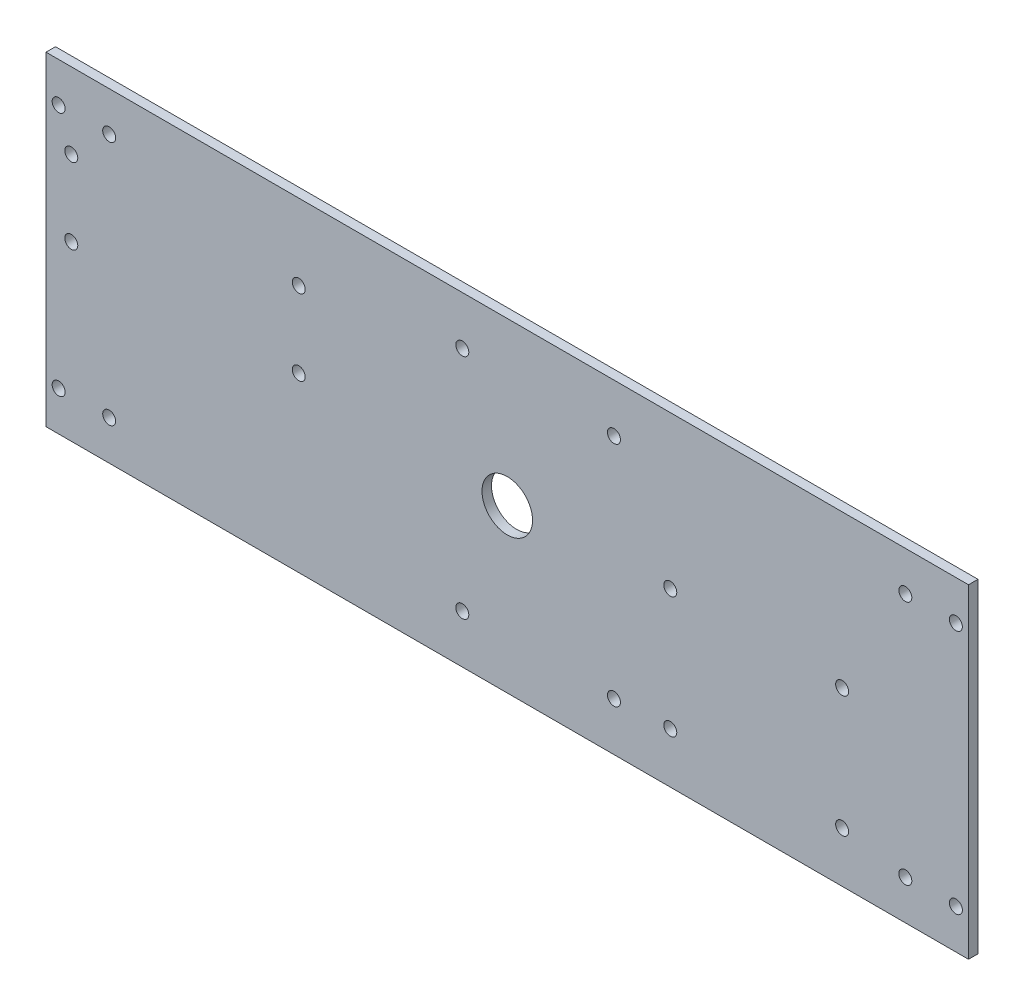
SolidWorks part; units mm, degrees
material "E-Glass Fiber"
ref_plane "Front Plane" through (0, 0, 0) normal (0, 0, 1) x (1, 0, 0)
ref_plane "Top Plane" through (0, 0, 0) normal (0, 1, 0) x (1, 0, 0)
ref_plane "Right Plane" through (0, 0, 0) normal (1, 0, 0) x (0, 0, -1)
sketch "Sketch1" plane through (0, 0, 0) normal (0, 0, 1) x (1, 0, 0)
  line L1 (-115.8875, -40.748) -> (115.8875, -40.748)
  line L2 (-115.8875, -40.748) -> (-115.8875, 40.7479)
  line L3 (-115.8875, 40.7479) -> (115.8875, 40.7479)
  line L4 (115.8875, -40.748) -> (115.8875, 40.7479)
  line L5 (-115.8875, -40.748) -> (115.8875, 40.7479) construction
  line L6 (-115.8875, 40.7479) -> (115.8875, -40.748) construction
  point P0 (0, 0)
  dimension "D1" = 231.775
  dimension "D2" = 81.4959
extrude "Boss-Extrude1" add sketch "Sketch1" along normal blind 2.3813
sketch "Sketch2" plane through (0, 0, 2.3813) normal (0, 0, 1) x (1, 0, 0)
  line L0 (-11.2979, 28.575) -> (26.8021, 28.575) construction
  line L1 (-115.8875, 0) -> (-111.125, 0) construction
  line L3 (-115.8875, 40.7479) -> (-115.8875, -40.748) construction
  line L4 (-111.125, 0) -> (-111.125, 9.525) construction
  line L5 (-111.125, 9.525) -> (-111.125, 25.4) construction
  line L6 (115.8875, 0) -> (111.125, 0) construction
  line L7 (115.8875, -40.748) -> (115.8875, 40.7479) construction
  line L8 (111.125, 0) -> (111.125, 9.525) construction
  line L9 (111.125, 9.525) -> (111.125, 25.4) construction
  line L10 (-112.7125, 40.7479) -> (-112.7125, 30.8204) construction
  line L11 (115.8875, 40.7479) -> (-115.8875, 40.7479) construction
  line L12 (-112.7125, 30.8204) -> (-100.0125, 30.8204) construction
  line L13 (-112.7125, 30.8204) -> (-115.8875, 30.8204) construction
  dimension "D1" = 38.1
  dimension "D2" = 28.575
  dimension "D3" = 11.2979
  dimension "D4" = 9.525
  dimension "D5" = 25.4
  dimension "D6" = 4.7625
  dimension "D7" = 3.175
  dimension "D8" = 30.8204
  dimension "D9" = 12.7
hole_wizard "#4 Clearance Hole1" positions "Sketch4" profile "Sketch5" hole size "#4" standard "ANSI Inch" end condition through all
sketch "Sketch4" plane through (0, 0, 2.3813) normal (0, 0, 1) x (1, 0, 0)
  point P0 (-11.2979, 28.575)
  point P3 (26.8021, 28.575)
sketch "Sketch5" plane through (-11.2979, 28.575, 2.3813) normal (1, 0, 0) x (0, -1, 0)
  line L0 (0, 0) -> (0, 2.3813)
  line L1 (0, 2.3813) -> (1.6319, 2.3813)
  line L2 (1.6319, 2.3813) -> (1.6319, 0)
  line L5 (1.6319, 0) -> (0, 0)
  line L11 (0, -6.35) -> (0, 107.95) construction
  dimension "Thru Hole Dia." = 3.2639
  dimension "Thru Hole Depth" = 2.3813
mirror "Mirror1" about plane through (0, 0, 0) normal (0, 1, 0) of "#4 Clearance Hole1"
hole_wizard "#4 Clearance Hole2" positions "Sketch7" profile "Sketch6" hole size "#4" standard "ANSI Inch"
sketch "Sketch7" plane through (0, 0, 2.3813) normal (0, 0, 1) x (1, 0, 0)
  point P0 (-112.7125, 30.8204)
  point P3 (-100.0125, 30.8204)
sketch "Sketch6" plane through (-112.7125, 30.8204, 2.3813) normal (1, 0, 0) x (0, -1, 0)
  line L0 (0, 0) -> (0, 10.5056)
  line L1 (0, 10.5056) -> (1.6319, 9.525)
  line L2 (1.6319, 9.525) -> (1.6319, 0)
  line L5 (1.6319, 0) -> (0, 0)
  line L10 (0, 10.5056) -> (-1.632, 9.525) construction
  line L11 (0, -6.35) -> (0, 107.95) construction
  dimension "Hole Dia." = 3.2639
  dimension "Hole Depth" = 9.525
  dimension "Drill Angle" = 118
mirror "Mirror2" about plane through (0, 0, 0) normal (1, 0, 0) of "#4 Clearance Hole2"
mirror "Mirror3" about plane through (0, 0, 0) normal (0, 1, 0) of "Mirror2"
hole_wizard "1/2 (0.5) Diameter Hole1" positions "Sketch9" profile "Sketch8" hole size "1/2" standard "ANSI Inch" end condition through all
sketch "Sketch9" plane through (0, 0, 2.3813) normal (0, 0, 1) x (1, 0, 0)
  point P0 (0, 0)
sketch "Sketch8" plane through (0, 0, 2.3813) normal (1, 0, 0) x (0, -1, 0)
  line L0 (0, 0) -> (0, 2.3812)
  line L1 (0, 2.3812) -> (6.35, 2.3812)
  line L2 (6.35, 2.3812) -> (6.35, 0)
  line L5 (6.35, 0) -> (0, 0)
  line L11 (0, -6.35) -> (0, 107.95) construction
  dimension "Thru Hole Dia." = 12.7
  dimension "Thru Hole Depth" = 2.3813
sketch "Sketch10" plane through (0, 0, 2.3813) normal (0, 0, 1) x (1, 0, 0)
  line L0 (-115.8875, 40.7479) -> (-115.8875, -40.748) construction
  line L1 (-109.5375, 21.6979) -> (-52.3875, 21.6979) construction
  line L2 (-109.5375, 21.6979) -> (-109.5375, 2.6479) construction
  line L3 (-109.5375, 2.6479) -> (-52.3875, 2.6479) construction
  line L4 (-52.3875, 21.6979) -> (-52.3875, 2.6479) construction
  line L5 (115.8875, 40.7479) -> (-115.8875, 40.7479) construction
  line L6 (-115.8875, -40.748) -> (115.8875, -40.748) construction
  line L7 (40.9575, -28.048) -> (84.1375, -28.048)
  line L8 (40.9575, -28.048) -> (40.9575, 2.432)
  line L9 (40.9575, 2.432) -> (84.1375, 2.432)
  line L10 (84.1375, -28.048) -> (84.1375, 2.432)
  line L11 (40.9575, -28.048) -> (84.1375, 2.432) construction
  line L12 (40.9575, 2.432) -> (84.1375, -28.048) construction
  line L13 (115.8875, -40.748) -> (115.8875, 40.7479) construction
  point P8 (62.5475, -12.808)
  dimension "D1" = 57.15
  dimension "D2" = 19.05
  dimension "D3" = 6.35
  dimension "D4" = 19.05
  dimension "D5" = 30.48
  dimension "D6" = 43.18
  dimension "D7" = 12.7
  dimension "D8" = 31.75
hole_wizard "#4 Clearance Hole3" positions "Sketch12" profile "Sketch11" hole size "#4" standard "ANSI Inch" end condition through all
sketch "Sketch12" plane through (0, 0, 2.3813) normal (0, 0, 1) x (1, 0, 0)
  point P0 (-109.5375, 21.6979)
  point P3 (-109.5375, 2.6479)
  point P6 (-52.3875, 2.6479)
  point P9 (-52.3875, 21.6979)
  point P13 (40.9575, 2.432)
  point P16 (84.1375, 2.432)
  point P19 (84.1375, -28.048)
  point P22 (40.9575, -28.048)
sketch "Sketch11" plane through (-109.5375, 21.6979, 2.3813) normal (1, 0, 0) x (0, -1, 0)
  line L0 (0, 0) -> (0, 2.3813)
  line L1 (0, 2.3813) -> (1.6319, 2.3813)
  line L2 (1.6319, 2.3813) -> (1.6319, 0)
  line L5 (1.6319, 0) -> (0, 0)
  line L11 (0, -6.35) -> (0, 107.95) construction
  dimension "Thru Hole Dia." = 3.2639
  dimension "Thru Hole Depth" = 2.3813
